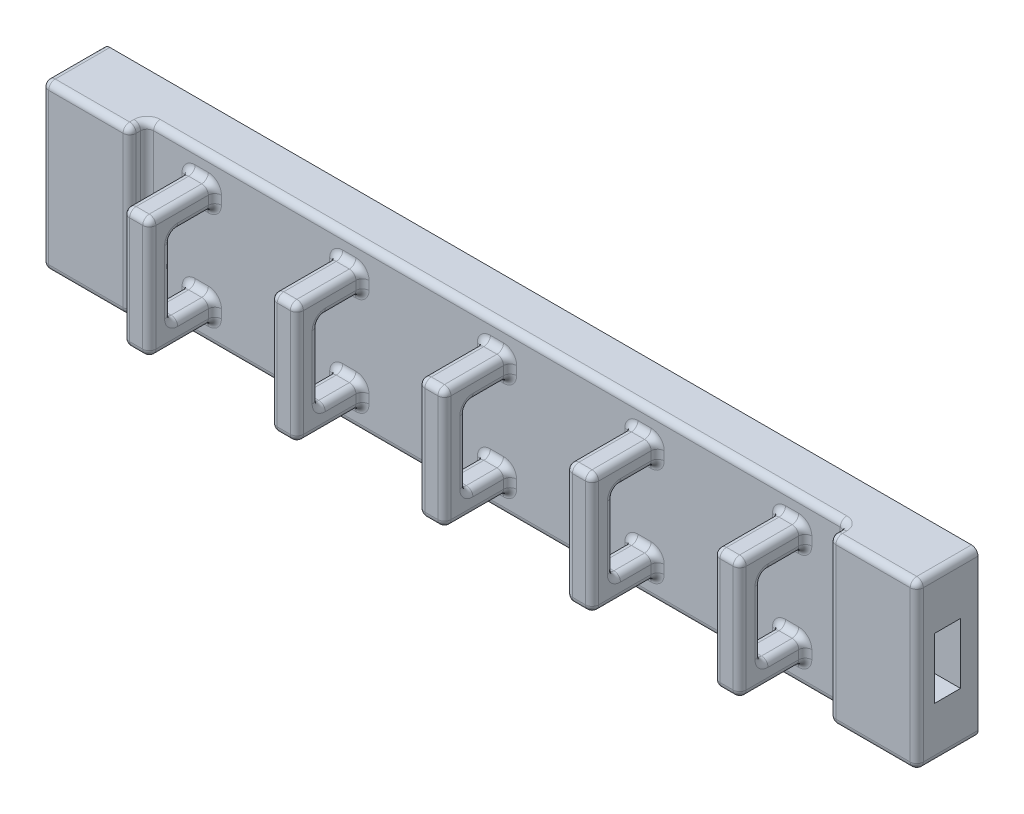
SolidWorks part; units mm, degrees
ref_plane "Front Plane" through (0, 0, 0) normal (0, 0, 1) x (1, 0, 0)
ref_plane "Top Plane" through (0, 0, 0) normal (0, 1, 0) x (1, 0, 0)
ref_plane "Right Plane" through (0, 0, 0) normal (1, 0, 0) x (0, 0, -1)
sketch "Sketch2" plane through (0, 0, 0) normal (0, 0, 1) x (1, 0, 0)
  line L1 (0, 0) -> (101.6, 0)
  line L2 (0, 0) -> (0, 19.05)
  line L3 (0, 19.05) -> (101.6, 19.05)
  line L4 (101.6, 0) -> (101.6, 19.05)
  dimension "D1" = 101.6
  dimension "D2" = 19.05
extrude "Boss-Extrude1" add sketch "Sketch2" along normal blind 5.08
hole_wizard "M3 Clearance Hole1" positions "Sketch3" profile "Sketch4" hole size "M3" standard "ANSI Metric" end condition through all
sketch "Sketch3" plane through (0, 0, 5.08) normal (0, 0, 1) x (1, 0, 0)
  line L0 (0, 19.05) -> (0, 0) construction
  line L1 (101.6, 0) -> (101.6, 19.05) construction
  line L2 (0, 0) -> (101.6, 0) construction
  point P0 (5.08, 9.525)
  point P2 (96.52, 9.525)
  dimension "D1" = 5.08
  dimension "D2" = 5.08
  dimension "D3" = 9.525
sketch "Sketch4" plane through (5.08, 9.525, 5.08) normal (1, 0, 0) x (0, -1, 0)
  line L0 (0, 0) -> (0, 5.08)
  line L1 (0, 5.08) -> (1.8, 5.08)
  line L2 (1.8, 5.08) -> (1.8, 0)
  line L5 (1.8, 0) -> (0, 0)
  line L11 (0, -6.35) -> (0, 107.95) construction
  dimension "Thru Hole Dia." = 3.6
  dimension "Thru Hole Depth" = 5.08
ref_plane "Plane2" through (16.51, 0, 0) normal (-1, 0, 0) x (0, 0, 1)
sketch "Sketch6" plane through (16.51, 0, 0) normal (-1, 0, 0) x (0, 0, 1)
  line L0 (5.08, 16.51) -> (12.7, 16.51)
  line L1 (12.7, 16.51) -> (12.7, 2.54)
  line L2 (12.7, 2.54) -> (5.08, 2.54)
  line L3 (5.08, 19.05) -> (5.08, 0) construction
  line L4 (5.08, 2.54) -> (5.08, 5.08)
  line L5 (5.08, 5.08) -> (10.16, 5.08)
  line L6 (10.16, 5.08) -> (10.16, 13.97)
  line L7 (10.16, 13.97) -> (5.08, 13.97)
  line L8 (5.08, 13.97) -> (5.08, 16.51)
  line L9 (5.08, 19.05) -> (0, 19.05) construction
  point P2 (5.08, 9.525)
  point P11 (10.16, 9.525)
  dimension "D1" = 2.54
  dimension "D2" = 2.54
  dimension "D3" = 2.54
  dimension "D4" = 5.08
extrude "Boss-Extrude3" add sketch "Sketch6" along normal blind 1.524 and the other way blind 1.524
fillet "Fillet2" radius 0.762 24 edges at (16.51, 16.51, 5.08) (16.51, 2.54, 5.08) (16.51, 5.08, 5.08) (16.51, 13.97, 5.08) (16.51, 13.97, 10.16) (16.51, 5.08, 10.16) (18.034, 13.97, 7.62) (18.034, 9.525, 10.16) (18.034, 5.08, 7.62) (18.034, 3.81, 5.08) (18.034, 2.54, 8.89) (18.034, 9.525, 12.7) (18.034, 16.51, 8.89) (18.034, 15.24, 5.08) (14.986, 16.51, 8.89) (14.986, 9.525, 12.7) (14.986, 2.54, 8.89) (14.986, 3.81, 5.08) (14.986, 5.08, 7.62) (14.986, 9.525, 10.16) (14.986, 13.97, 7.62) (14.986, 15.24, 5.08) (16.51, 2.54, 12.7) (16.51, 16.51, 12.7)
pattern_linear "LPattern2" count 5 spacing 17.145 along (1, 0, 0) of "Boss-Extrude3", "Fillet2"
sketch "Sketch7" plane through (0, 0, 5.08) normal (0, 0, -1) x (-1, 0, 0)
  line L1 (-96.52, 6.0055) -> (-93.472, 7.7652)
  line L2 (-93.472, 7.7652) -> (-93.472, 11.2848)
  line L3 (-93.472, 11.2848) -> (-96.52, 13.0445)
  line L4 (-96.52, 13.0445) -> (-98.044, 12.1646) construction
  line L5 (-99.568, 11.2848) -> (-99.568, 9.525) construction
  line L6 (-98.044, 6.8854) -> (-96.52, 6.0055) construction
  line L7 (-96.52, 13.0445) -> (-101.6, 13.0445)
  line L8 (-8.128, 7.7652) -> (-5.08, 6.0055)
  line L9 (-5.08, 6.0055) -> (-3.556, 6.8854) construction
  line L10 (-2.032, 7.7652) -> (-2.032, 9.525) construction
  line L11 (-3.556, 12.1646) -> (-5.08, 13.0445) construction
  line L12 (-5.08, 13.0445) -> (-8.128, 11.2848)
  line L13 (-8.128, 11.2848) -> (-8.128, 7.7652)
  line L14 (-101.6, 0) -> (-101.6, 19.05) construction
  line L15 (-101.6, 13.0445) -> (-101.6, 6.0055)
  line L16 (-101.6, 6.0055) -> (-96.52, 6.0055)
  line L17 (-5.08, 13.0445) -> (0, 13.0445)
  line L18 (0, 19.05) -> (0, 0) construction
  line L19 (0, 13.0445) -> (0, 6.0055)
  line L20 (0, 6.0055) -> (-5.08, 6.0055)
  line L21 (-2.032, 11.2848) -> (-3.556, 12.1646) construction
  line L22 (-2.032, 9.525) -> (-2.032, 11.2848) construction
  line L23 (-3.556, 6.8854) -> (-2.032, 7.7652) construction
  line L24 (-99.568, 9.525) -> (-99.568, 7.7652) construction
  line L25 (-98.044, 12.1646) -> (-99.568, 11.2848) construction
  line L26 (-99.568, 7.7652) -> (-98.044, 6.8854) construction
  circle A0 centre (-96.52, 9.525) radius 3.048 construction
  circle A1 centre (-5.08, 9.525) radius 3.048 construction
  dimension "D1" = 6.096
extrude "Cut-Extrude1" cut sketch "Sketch7" along normal blind 3.048
sketch "Sketch8" plane through (0, 0, 5.08) normal (0, 0, 1) x (1, 0, 0)
  line L0 (101.6, 19.05) -> (0, 19.05) construction
  line L1 (0, 0) -> (10.16, 0)
  line L2 (0, 0) -> (0, 19.05)
  line L3 (0, 19.05) -> (10.16, 19.05)
  line L4 (10.16, 0) -> (10.16, 19.05)
  line L6 (101.6, 0) -> (91.44, 0)
  line L7 (101.6, 0) -> (101.6, 19.05)
  line L8 (101.6, 19.05) -> (91.44, 19.05)
  line L9 (91.44, 0) -> (91.44, 19.05)
  dimension "D1" = 10.16
extrude "Boss-Extrude4" add sketch "Sketch8" along normal blind 2.032
fillet "Fillet3" radius 0.762 20 edges at (50.8, 0, 5.08) (50.8, 19.05, 5.08) (10.16, 0, 6.096) (91.44, 0, 6.096) (10.16, 19.05, 6.096) (91.44, 19.05, 6.096) (5.08, 19.05, 7.112) (10.16, 9.525, 7.112) (5.08, 0, 7.112) (0, 9.525, 7.112) (96.52, 0, 7.112) (91.44, 9.525, 7.112) (96.52, 19.05, 7.112) (101.6, 9.525, 7.112) (10.16, 9.525, 5.08) (91.44, 9.525, 5.08) (0, 0, 3.556) (0, 19.05, 3.556) (101.6, 0, 3.556) (101.6, 19.05, 3.556)
